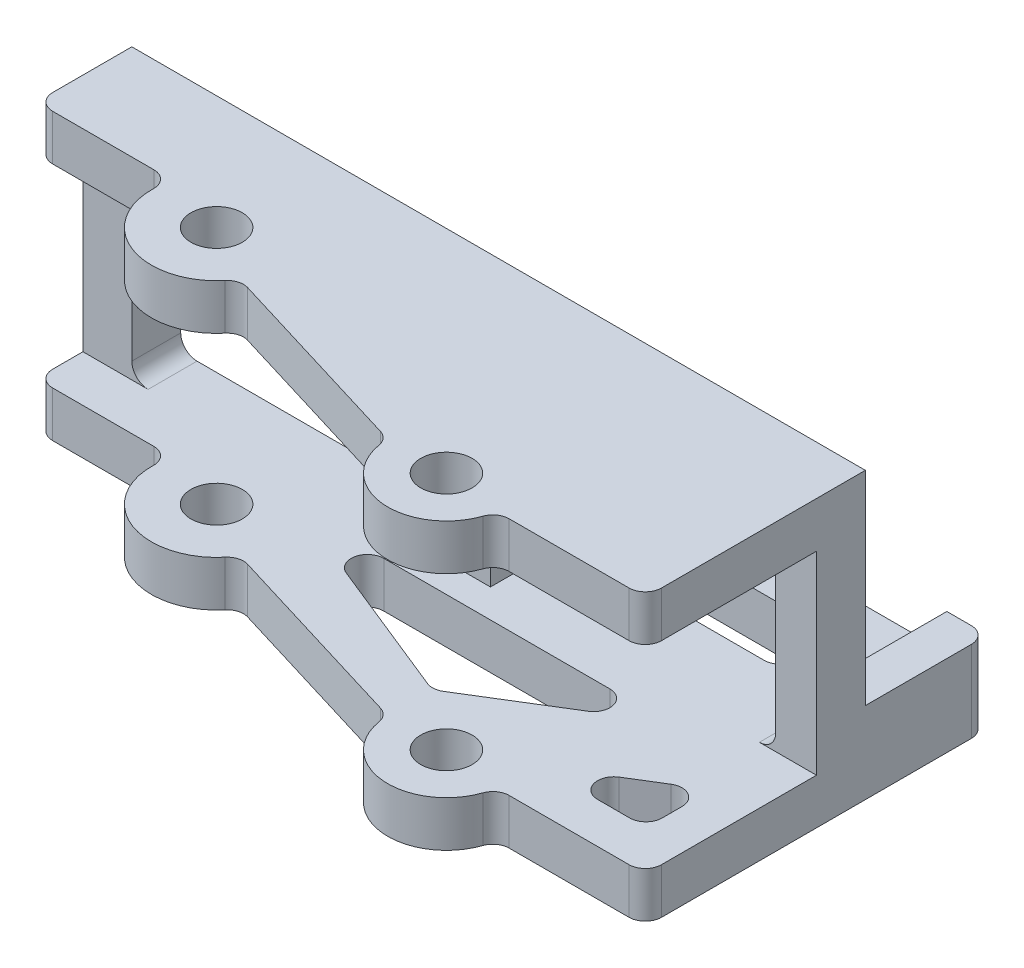
SolidWorks part; units mm, degrees
ref_plane "Front Plane" through (0, 0, 0) normal (0, 0, 1) x (1, 0, 0)
ref_plane "Top Plane" through (0, 0, 0) normal (0, 1, 0) x (1, 0, 0)
ref_plane "Right Plane" through (0, 0, 0) normal (1, 0, 0) x (0, 0, -1)
sketch "Sketch1" plane through (0, 0, 0) normal (0, 0, 1) x (1, 0, 0)
  line L1 (57.15, 22.225) -> (-57.15, 22.225)
  line L2 (57.15, 22.225) -> (57.15, -22.225)
  line L3 (57.15, -22.225) -> (-57.15, -22.225)
  line L4 (-57.15, 22.225) -> (-57.15, -22.225)
  line L5 (57.15, 22.225) -> (-57.15, -22.225) construction
  line L6 (57.15, -22.225) -> (-57.15, 22.225) construction
  point P0 (0, 0)
  dimension "D1" = 44.45
  dimension "D2" = 114.3
extrude "Boss-Extrude1" add sketch "Sketch1" along normal mid plane 62.23
sketch "Sketch3" plane through (0, -22.225, 0) normal (0, -1, 0) x (1, 0, 0)
  line L0 (57.15, -12.065) -> (-57.15, -12.065) construction
  line L1 (57.15, 31.115) -> (57.15, -31.115) construction
  line L2 (-57.15, 31.115) -> (-57.15, -31.115) construction
  line L3 (-57.15, -31.115) -> (57.15, -31.115) construction
  circle A0 centre (-26.162, 5.715) radius 4
  circle A1 centre (24.892, 20.955) radius 4
  dimension "D2" = 33.02
  dimension "D3" = 32.258
  dimension "D4" = 8
  dimension "D6" = 8
  dimension "D7" = 51.054
  dimension "D1" = 19.05
  dimension "D5" = 15.24
extrude "Pivot Points" cut sketch "Sketch3" against normal through all
sketch "Sketch4" plane through (0, 0, 31.115) normal (0, 0, 1) x (1, 0, 0)
  line L0 (57.15, -22.225) -> (57.15, 22.225) construction
  line L1 (-57.15, -15.113) -> (57.15, -15.113)
  line L2 (-57.15, -15.113) -> (-57.15, 15.113)
  line L3 (-57.15, 15.113) -> (57.15, 15.113)
  line L4 (57.15, -15.113) -> (57.15, 15.113)
  line L5 (-57.15, -15.113) -> (57.15, 15.113) construction
  line L6 (-57.15, 15.113) -> (57.15, -15.113) construction
  line L7 (57.15, 22.225) -> (-57.15, 22.225) construction
  point P0 (0, 0)
  dimension "D1" = 7.112
extrude "Top Cutout" cut sketch "Sketch4" against normal blind 35.56
sketch "Sketch5" plane through (0, 0, -31.115) normal (0, 0, -1) x (-1, 0, 0)
  line L0 (57.15, 22.225) -> (57.15, -22.225) construction
  line L1 (-57.15, 22.225) -> (57.15, 22.225)
  line L2 (-57.15, 22.225) -> (-57.15, -9.525)
  line L3 (-57.15, -9.525) -> (57.15, -9.525)
  line L4 (57.15, 22.225) -> (57.15, -9.525)
  line L5 (57.15, -22.225) -> (-57.15, -22.225) construction
  dimension "D1" = 12.7
extrude "Bottom Cutout" cut sketch "Sketch5" against normal blind 19.05
sketch "Sketch6" plane through (0, -22.225, 0) normal (0, -1, 0) x (1, 0, 0)
  line L0 (-17.4059, 10.8682) -> (15.748, 20.955)
  line L1 (33.9474, 22.225) -> (57.15, 22.225)
  line L2 (57.15, 31.115) -> (57.15, -31.115) construction
  line L3 (-35.8959, 2.8036) -> (-57.15, 2.8036)
  line L4 (-57.15, 31.115) -> (-57.15, -31.115) construction
  line L5 (-57.15, 2.8036) -> (-57.15, 31.115)
  line L6 (-57.15, 31.115) -> (57.15, 31.115)
  line L7 (57.15, 31.115) -> (57.15, 22.225)
  line L8 (-57.15, -12.065) -> (-21.59, -12.065)
  line L9 (-21.59, -12.065) -> (-4.826, -31.115)
  line L10 (-57.15, -31.115) -> (57.15, -31.115) construction
  line L11 (-4.826, -31.115) -> (-57.15, -31.115)
  line L12 (-57.15, -31.115) -> (-57.15, -12.065)
  circle A0 centre (24.892, 20.955) radius 9.144 construction
  circle A1 centre (-26.162, 5.715) radius 10.16 construction
  arc A2 (15.748, 20.955) -> (33.9474, 22.225) centre (24.892, 20.955) cw
  arc A3 (-35.8959, 2.8036) -> (-17.4059, 10.8682) centre (-26.162, 5.715) cw
  point P22 (15.748, 20.955)
  line M8 (-57.15, -31.115) -> (57.15, -31.115)
  line M9 (57.15, -31.115) -> (57.15, 31.115)
  line M10 (57.15, 31.115) -> (-57.15, 31.115)
  line M11 (-57.15, 31.115) -> (-57.15, -31.115)
  dimension "D1" = 18.288
  dimension "D2" = 20.32
  dimension "D7" = 34.6543
  dimension "D3" = 35.56
  dimension "D4" = 52.324
  dimension "D5" = 19.05
  dimension "D6" = 21.2541
  dimension "D8" = 8.89
extrude "Side Profile Cut" cut sketch "Sketch6" against normal through all contours L3 A3 L0 A2 L1 M9 M10 M11 | L9 L8 M11 M8
sketch "Sketch9" plane through (0, -22.225, 0) normal (0, -1, 0) x (-1, 0, 0)
  line L11 (-48.26, 21.59) -> (2.54, 21.59)
  line L13 (57.15, 12.065) -> (21.59, 12.065) construction
  line L14 (-57.15, -22.225) -> (-57.15, 31.115) construction
  point P0 (2.54, 21.59)
  point P2 (-48.26, 21.59)
  dimension "D1" = 50.8
  dimension "D2" = 9.525
  dimension "D3" = 8.89
hole_wizard "#8 Clearance Hole1" positions "Sketch9" profile "Sketch8" hole size "#8" standard "ANSI Inch" end condition through all
sketch "Sketch8" plane through (-2.54, -22.225, -21.59) normal (1, 0, 0) x (0, 0, -1)
  line L0 (0, 0) -> (0, 44.45)
  line L1 (0, 44.45) -> (2.2479, 44.45)
  line L2 (2.2479, 44.45) -> (2.2479, 0)
  line L5 (2.2479, 0) -> (0, 0)
  line L11 (0, -6.35) -> (0, 107.95) construction
  dimension "Thru Hole Dia." = 4.4958
  dimension "Thru Hole Depth" = 44.45
sketch "Sketch10" plane through (0, -22.225, 0) normal (0, -1, 0) x (1, 0, 0)
  line L0 (34.3959, 15.875) -> (50.9059, 15.875)
  line L1 (50.9059, 15.875) -> (50.9059, 5.715)
  line L2 (50.9059, 5.715) -> (34.3959, 15.875)
  line L3 (2.54, -15.875) -> (43.18, -15.875)
  line L4 (43.18, -15.875) -> (35.3562, -24.765)
  line L5 (35.3562, -24.765) -> (10.3632, -24.765)
  line L6 (10.3632, -24.765) -> (2.54, -15.875)
  line L7 (33.9474, 22.225) -> (57.15, 22.225) construction
  line L8 (42.6509, 15.875) -> (42.6509, 22.225) construction
  line L9 (50.9059, 10.795) -> (57.15, 10.795) construction
  line L10 (57.15, 22.225) -> (57.15, -31.115) construction
  line L11 (-18.8943, 0) -> (38.3839, 0)
  line L12 (38.3839, 0) -> (15.6827, 13.97)
  line L13 (15.6827, 13.97) -> (-18.8943, 0)
  line L16 (-21.59, -12.065) -> (-4.826, -31.115) construction
  line L17 (-4.826, -31.115) -> (57.15, -31.115) construction
  line L18 (-2.54, -21.59) -> (48.26, -21.59) construction
  line L19 (-57.15, -12.065) -> (-21.59, -12.065) construction
  circle A0 centre (-2.54, -21.59) radius 2.2479 construction
  circle A1 centre (48.26, -21.59) radius 2.2479 construction
  point P20 (22.86, -21.59)
  point P21 (22.86, -15.875)
  dimension "D1" = 6.35
  dimension "D2" = 6.2441
  dimension "D3" = 10.16
  dimension "D4" = 22
  dimension "D5" = 131.348
  dimension "D6" = 131.35
  dimension "D7" = 6.35
  dimension "D8" = 40.64
  dimension "D9" = 3.81
  dimension "D10" = 13.97
  dimension "D11" = 11.43
  dimension "D12" = 16.51
extrude "optimization cutouts" cut sketch "Sketch10" along direction (0, -1, 0) on the side against the normal up to next (12.7 mm away)
sketch "Sketch12" plane through (0, 0, -4.445) normal (0, 0, 1) x (1, 0, 0)
  line L0 (57.15, 15.113) -> (-57.15, 15.113) construction
  line L1 (50.8, 15.113) -> (6.35, 15.113)
  line L2 (50.8, 15.113) -> (50.8, -15.113)
  line L3 (50.8, -15.113) -> (6.35, -15.113)
  line L4 (6.35, 15.113) -> (6.35, -15.113)
  line L5 (-57.15, 15.113) -> (-57.15, -15.113) construction
  line L6 (-5.08, -15.113) -> (-49.53, -15.113)
  line L7 (-5.08, -15.113) -> (-5.08, 15.113)
  line L8 (-5.08, 15.113) -> (-49.53, 15.113)
  line L9 (-49.53, -15.113) -> (-49.53, 15.113)
  line L10 (57.15, -15.113) -> (57.15, 15.113) construction
  line L11 (-35.8959, -15.113) -> (-57.15, -15.113) construction
  dimension ".3" = 7.62
  dimension "D2" = 6.35
  dimension "D4" = 44.45
extrude "Cut-Extrude7" cut sketch "Sketch12" against normal through all
fillet "Fillet2" radius 2.54 31 edges at (57.15, 18.669, 22.225) (33.9474, 18.669, 22.225) (15.748, 18.669, 20.955) (15.748, -18.669, 20.955) (33.9474, -18.669, 22.225) (57.15, -18.669, 22.225) (57.15, -15.875, -31.115) (-4.826, -15.875, -31.115) (-21.59, -18.669, -12.065) (-18.8943, -18.669, 0) (38.3839, -18.669, 0) (15.6827, -18.669, 13.97) (35.3562, -18.669, -24.765) (43.18, -18.669, -15.875) (2.54, -15.875, -15.875) (10.3632, -18.669, -24.765) (50.9059, -18.669, 15.875) (34.3959, -18.669, 15.875) (50.9059, -18.669, 5.715) (-17.4059, -18.669, 10.8682) (-17.4059, 18.669, 10.8682) (-35.8959, 18.669, 2.8036) (-35.8959, -18.669, 2.8036) (-57.15, 18.669, 2.8036) (-57.15, -18.669, 2.8036) (50.8, -15.113, -17.78) (-5.08, -15.113, -17.6357) (50.8, 15.113, -8.255) (-5.08, 15.113, -8.255) (-49.53, 15.113, -8.255) (-49.53, -15.113, -8.255)
